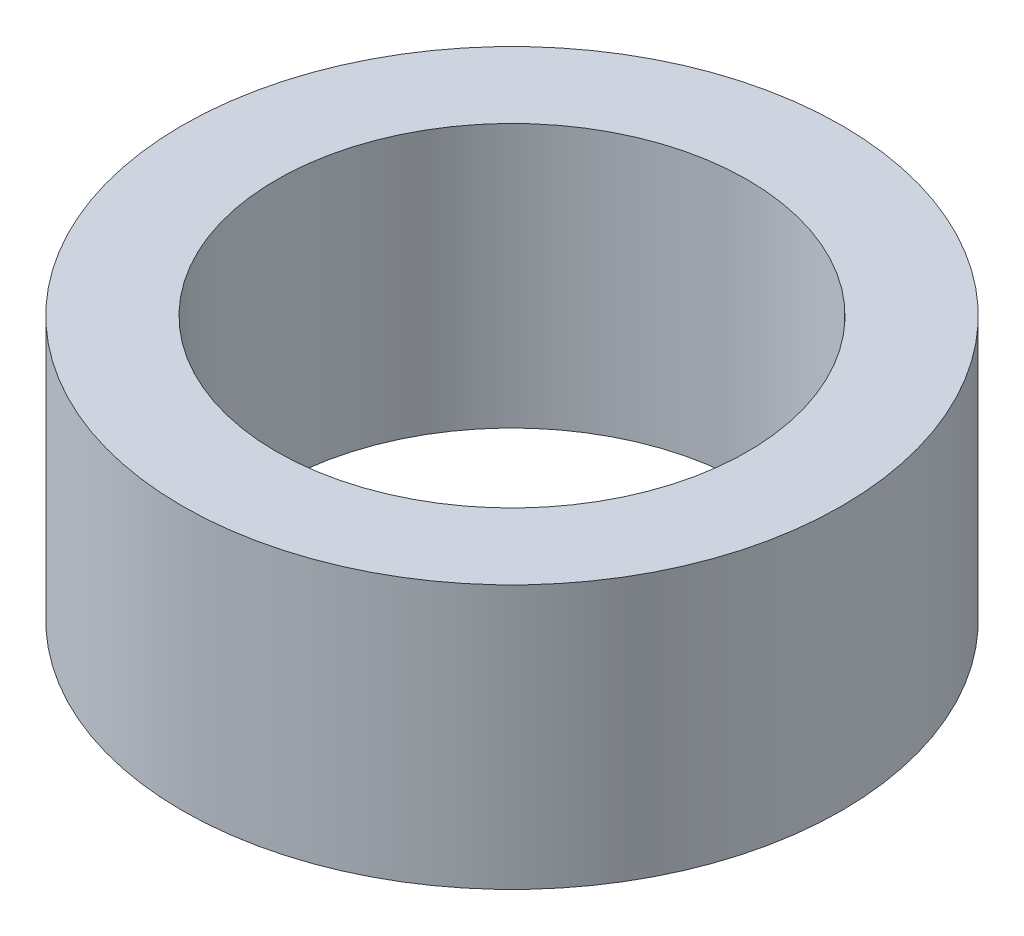
SolidWorks part; units mm, degrees
ref_plane "Front Plane" through (0, 0, 0) normal (0, 0, 1) x (1, 0, 0)
ref_plane "Top Plane" through (0, 0, 0) normal (0, 1, 0) x (1, 0, 0)
ref_plane "Right Plane" through (0, 0, 0) normal (1, 0, 0) x (0, 0, -1)
sketch "Sketch1" plane through (0, 0, 0) normal (0, 1, 0) x (1, 0, 0)
  circle A0 centre (0, 0) radius 35
  dimension "FLANGE_OD" = 70
extrude "Boss-Extrude1" add sketch "Sketch1" along normal blind 28
sketch "Sketch2" plane through (0, 0, 0) normal (0, 1, 0) x (1, 0, 0)
  circle A0 centre (0, 0) radius 25
  dimension "BORE_D" = 50
extrude "Cut-Extrude1" cut sketch "Sketch2" along normal through all
sketch "Sketch3" plane through (0, 28, 0) normal (0, 1, 0) x (1, 0, 0)
  circle A0 centre (0, 0) radius 14.5261 construction
  circle A1 centre (-14.5261, 0) radius 1.5993
  dimension "BOLT_D" = 3.1986
  dimension "BOLT_PCD" = 29.0521
extrude "Cut-Extrude2" cut sketch "Sketch3" against normal blind 26.9723 rebuild error yes
pattern_circular "CirPattern1" count 4 over 360 rebuild error yes
